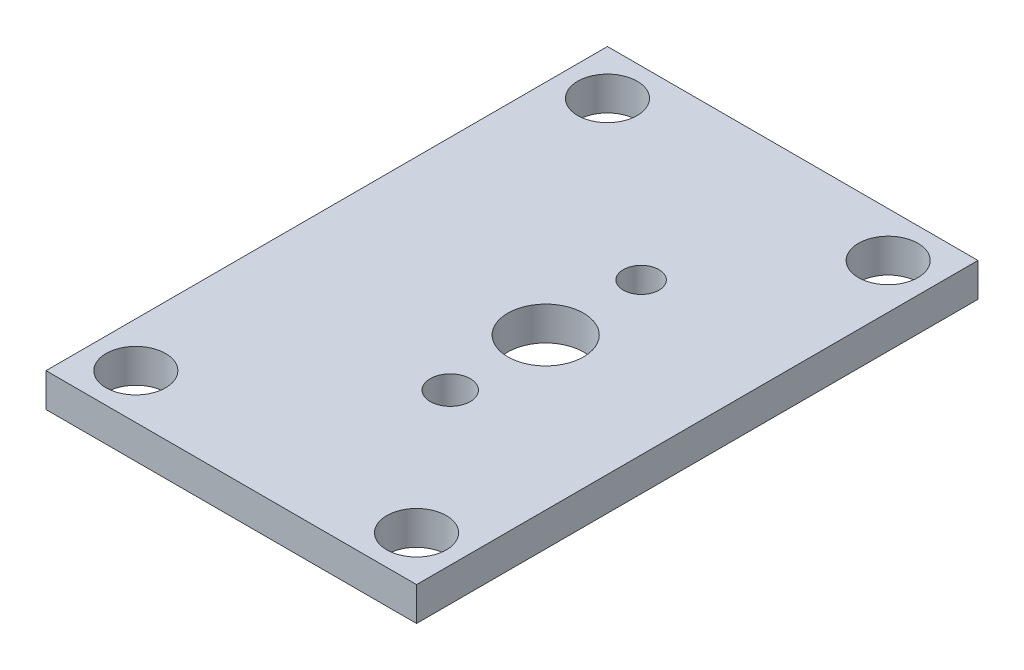
SolidWorks part; units mm, degrees
ref_plane "Front Plane" through (0, 0, 0) normal (0, 0, 1) x (1, 0, 0)
ref_plane "Top Plane" through (0, 0, 0) normal (0, 1, 0) x (1, 0, 0)
ref_plane "Right Plane" through (0, 0, 0) normal (1, 0, 0) x (0, 0, -1)
sketch "Sketch1" plane through (0, 0, 0) normal (0, 1, 0) x (1, 0, 0)
  line L1 (-10.223, 36.3848) -> (14.777, 36.3848)
  line L2 (-10.223, 36.3848) -> (-10.223, -13.6152)
  line L3 (-10.223, -13.6152) -> (14.777, -13.6152)
  line L4 (14.777, 36.3848) -> (14.777, -13.6152)
  circle A0 centre (1.277, 11.3848) radius 3.375
  dimension "D3" = 6.75
  dimension "D1" = 50
  dimension "D2" = 25
  dimension "D4" = 13.5
  dimension "D5" = 25
extrude "Boss-Extrude1" add sketch "Sketch1" along normal blind 3
sketch "Sketch2" plane through (-10.223, 0, 0) normal (-1, 0, 0) x (0, 0, 1)
  line L0 (18.15, 0) -> (-18.15, 0) construction
  line L1 (-36.3848, 3) -> (13.6152, 3)
  line L2 (-36.3848, 3) -> (-36.3848, 0)
  line L3 (-36.3848, 0) -> (13.6152, 0)
  line L4 (13.6152, 3) -> (13.6152, 0)
  line L5 (13.6152, 3) -> (13.6152, 0) construction
extrude "Boss-Extrude2" add sketch "Sketch2" along normal blind 8
sketch "Sketch3" plane through (0, 0, 0) normal (0, -1, 0) x (1, 0, 0)
  line L0 (-18.223, 13.6152) -> (14.777, 13.6152) construction
  line L1 (-18.223, -36.3848) -> (-10.223, -36.3848)
  line L2 (-18.223, -36.3848) -> (-18.223, 13.6152)
  line L3 (-18.223, 13.6152) -> (-10.223, 13.6152)
  line L4 (-10.223, -36.3848) -> (-10.223, 13.6152)
  dimension "D1" = 8
extrude "Boss-Extrude3" add sketch "Sketch3" along normal blind 42
sketch "Sketch4" plane through (0, 3, 0) normal (0, 1, 0) x (1, 0, 0)
  line L0 (-18.223, -13.6152) -> (-18.223, 36.3848) construction
  line L1 (14.777, 36.3848) -> (-18.223, 36.3848) construction
  line L2 (-18.223, -13.6152) -> (14.777, -13.6152) construction
  circle A0 centre (-14.223, 32.3848) radius 2.65
  circle A1 centre (-14.223, -9.6152) radius 2.65
  dimension "D2" = 5.3
  dimension "D4" = 5.3
  dimension "D5" = 4
  dimension "D6" = 4
  dimension "D1" = 4
  dimension "D3" = 4
extrude "Cut-Extrude1" cut sketch "Sketch4" against normal blind 3.3
ref_plane "Plane1" through (0, -19.5, 0) normal (0, 1, 0) x (1, 0, 0)
mirror "Mirror1" about plane through (0, -19.5, 0) normal (0, 1, 0) of "Cut-Extrude1"
sketch "Sketch5" plane through (-18.223, 0, 0) normal (-1, 0, 0) x (0, 0, 1)
  line L0 (18.15, 0) -> (-18.15, 0) construction
  line L1 (-6.9841, -24.1818) -> (-6.6547, -18.3888) construction
  line L2 (-6.6547, -18.3888) -> (-11.5069, -15.207) construction
  line L3 (-11.5069, -15.207) -> (-16.6885, -17.8182) construction
  line L4 (-16.6885, -17.8182) -> (-17.0179, -23.6112) construction
  line L5 (-17.0179, -23.6112) -> (-12.1657, -26.793) construction
  line L6 (-12.1657, -26.793) -> (-6.9841, -24.1818) construction
  circle A0 centre (-11.8363, -21) radius 5.025 construction
  circle A1 centre (-11.8363, -21) radius 5.8024
  dimension "D1" = 21
  dimension "D2" = 10.05
extrude "Cut-Extrude2" cut sketch "Sketch5" against normal blind 9
fillet "Fillet2" radius 1 1 edges at (-10.223, -21, -6.0339)
ref_plane "Plane2" through (-1.723, 0, 0) normal (-1, 0, 0) x (0, 0, 1)
mirror "Mirror2" about plane through (-1.723, 0, 0) normal (-1, 0, 0) of "Cut-Extrude1"
sketch "Sketch6" plane through (0, 3, 0) normal (0, 1, 0) x (1, 0, 0)
  line L0 (1.277, 14.7598) -> (1.277, 8.0098) construction
  line L1 (14.777, -13.6152) -> (14.777, 36.3848) construction
  line L2 (14.777, 17.202) -> (14.777, 5.5675)
  circle A0 centre (1.277, 11.3848) radius 3.375 construction
  circle A1 centre (1.277, 11.3848) radius 3.1
  circle A2 centre (1.277, 11.3848) radius 12.7
  arc A3 (14.777, 17.202) -> (14.777, 5.5675) centre (1.277, 11.3848) ccw
  line M9 (14.777, -13.6152) -> (14.777, 36.3848)
  dimension "D1" = 25.4
  dimension "D2" = 2
extrude "Boss-Extrude4" add sketch "Sketch6" along normal blind 2 contours A3 A2 M9
fillet "Fillet4" radius 1 1 edges at (14.777, 5, -11.3848)
sketch "Sketch8" plane through (0, 3, 0) normal (0, 1, 0) x (1, 0, 0)
  line L0 (4.652, 11.3848) -> (-2.098, 11.3848) construction
  circle A0 centre (1.277, 11.3848) radius 3.375 construction
  circle A1 centre (1.277, 19.8848) radius 1.5898
  circle A2 centre (1.277, 2.8848) radius 1.7774
  point P9 (1.277, 11.3848)
  dimension "D1" = 8.5
  dimension "D2" = 8.5
extrude "Cut-Extrude3" cut sketch "Sketch8" against normal blind 10
sketch "Sketch9" plane through (0, 0, 13.6152) normal (0, 0, 1) x (1, 0, 0)
  line L0 (-18.223, -42) -> (-18.223, 3) construction
  line L1 (-18.223, 0) -> (-10.223, 0)
  line L2 (-18.223, 0) -> (-18.223, -42)
  line L3 (-18.223, -42) -> (-10.223, -42)
  line L4 (-10.223, 0) -> (-10.223, -42)
extrude "Cut-Extrude4" cut sketch "Sketch9" against normal through all
ref_plane "Plane3" through (0, 0, 13.6152) normal (0, 0, 1) x (1, 0, 0)
sketch "Sketch10" plane through (0, 0, 13.6152) normal (0, 0, 1) x (1, 0, 0)
  line L1 (-18.223, 3) -> (15.2949, 3)
  line L2 (-18.223, 3) -> (-18.223, 9.2123)
  line L3 (-18.223, 9.2123) -> (15.2949, 9.2123)
  line L4 (15.2949, 3) -> (15.2949, 9.2123)
extrude "Cut-Extrude5" cut sketch "Sketch10" against normal blind 55
